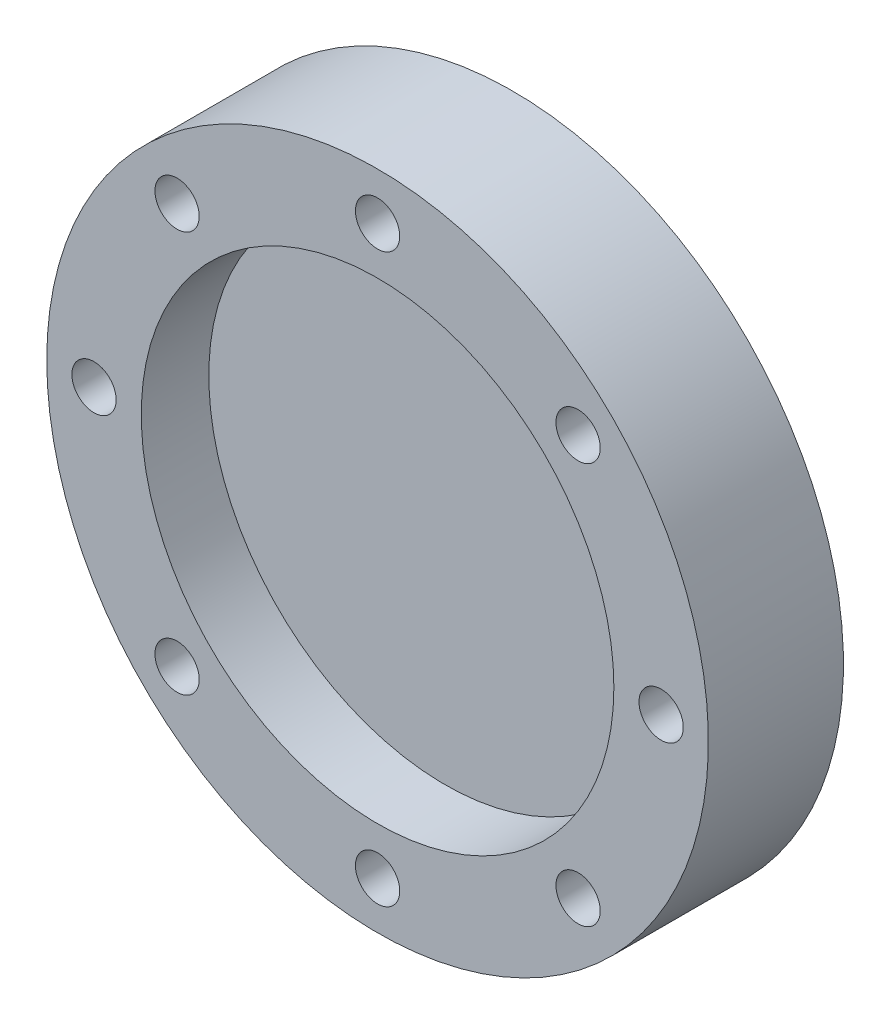
SolidWorks part; units mm, degrees
material "PLA (Polylactic Acid)"
ref_plane "Front Plane" through (0, 0, 0) normal (0, 0, 1) x (1, 0, 0)
ref_plane "Top Plane" through (0, 0, 0) normal (0, 1, 0) x (1, 0, 0)
ref_plane "Right Plane" through (0, 0, 0) normal (1, 0, 0) x (0, 0, -1)
sketch "Sketch2" plane through (0, 0, -1.7131) normal (0, 0, -1) x (-1, 0, 0)
  circle A0 centre (0, 0) radius 31.115
extrude "Boss-Extrude1" add sketch "Sketch2" along normal blind 12.7
sketch "Sketch3" plane through (0, 0, -14.4131) normal (0, 0, -1) x (-1, 0, 0)
  circle A0 centre (0, 26.67) radius 2.0828
  circle A3 centre (0, 26.67) radius 2.0828 construction
extrude "Cut-Extrude1" cut sketch "Sketch3" against normal up to surface (12.7 mm away) up to face at (-31.115, 0, -1.7131)
pattern_circular "CirPattern1" count 8 over 360 of "Cut-Extrude1"
sketch "Sketch4" plane through (0, 0, -1.7131) normal (0, 0, 1) x (1, 0, 0)
  circle A0 centre (0, 0) radius 22.225
  dimension "D1" = 44.45
extrude "Cut-Extrude2" cut sketch "Sketch4" against normal blind 6.35
